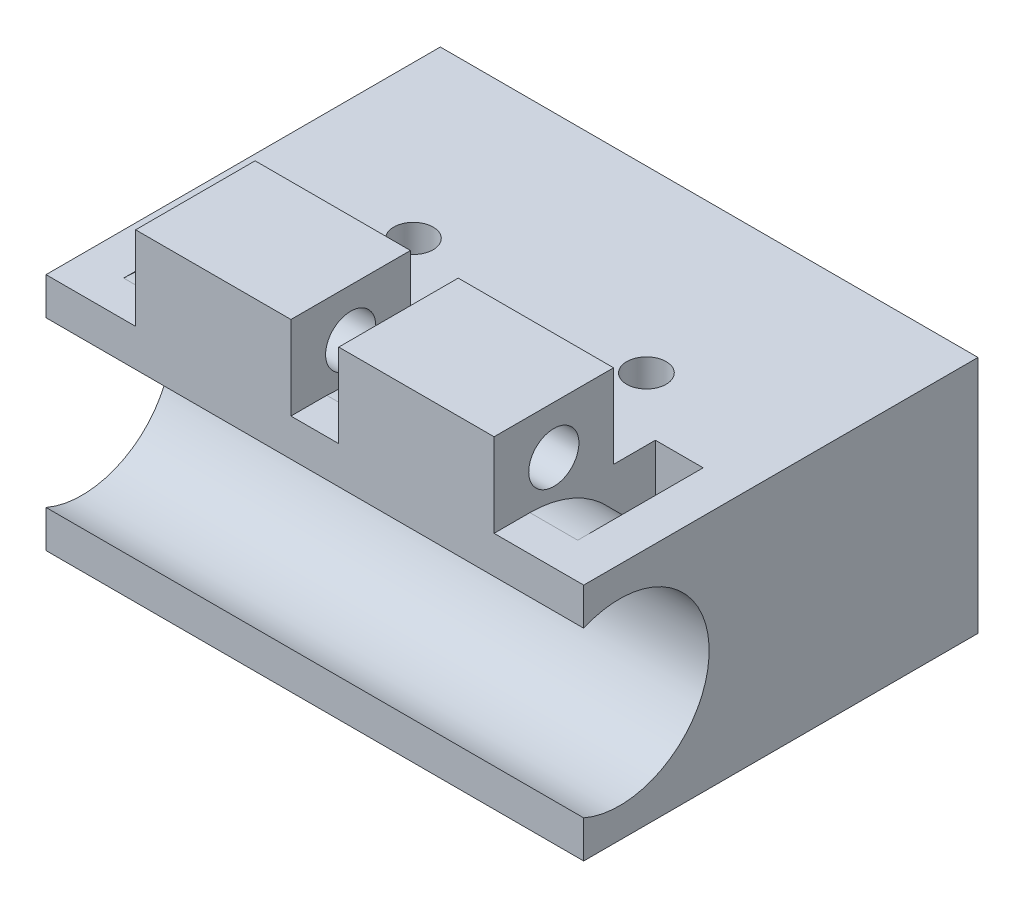
SolidWorks part; units mm, degrees
ref_plane "Front Plane" through (0, 0, 0) normal (0, 0, 1) x (1, 0, 0)
ref_plane "Top Plane" through (0, 0, 0) normal (0, 1, 0) x (1, 0, 0)
ref_plane "Right Plane" through (0, 0, 0) normal (1, 0, 0) x (0, 0, -1)
sketch "Sketch2" plane through (0, 0, 0) normal (0, 0, 1) x (1, 0, 0)
  line L1 (22.5, 10) -> (-22.5, 10)
  line L2 (22.5, 10) -> (22.5, -10)
  line L3 (22.5, -10) -> (-22.5, -10)
  line L4 (-22.5, 10) -> (-22.5, -10)
  line L5 (22.5, 10) -> (-22.5, -10) construction
  line L6 (22.5, -10) -> (-22.5, 10) construction
  point P0 (0, 0)
  dimension "D1" = 20
  dimension "D2" = 45
extrude "Boss-Extrude1" add sketch "Sketch2" along normal blind 33
sketch "Sketch3" plane through (22.5, 0, 0) normal (1, 0, 0) x (0, 0, -1)
  line L0 (-30, 0) -> (0, 0) construction
  circle A0 centre (-30, 0) radius 7.5
  dimension "D1" = 15
  dimension "D2" = 30
extrude "Cut-Extrude1" cut sketch "Sketch3" against normal blind 45
sketch "Sketch4" plane through (0, 0, 0) normal (0, 0, -1) x (-1, 0, 0)
  line L4 (22.5, -10) -> (22.5, 10)
  line L5 (22.5, 10) -> (-22.5, 10)
  line L6 (-22.5, 10) -> (-22.5, -10)
  line L7 (-22.5, -10) -> (22.5, -10)
  line L8 (22.5, -10) -> (22.5, 10)
  line L9 (22.5, 10) -> (-22.5, 10)
  line L10 (-22.5, 10) -> (-22.5, -10)
  line L11 (-22.5, -10) -> (22.5, -10)
  circle A0 centre (-15, 0) radius 4
  circle A1 centre (15, 0) radius 4
  dimension "D2" = 8
  dimension "D3" = 30
  dimension "D4" = 15
  dimension "D1" = 0
extrude "Cut-Extrude2" cut sketch "Sketch4" against normal blind 10 contours A0 | A1 region at (15, 0, 0) region at (-15, 0, 0)
sketch "Sketch5" plane through (0, -10, 0) normal (0, -1, 0) x (1, 0, 0)
  line L0 (0, 19.5) -> (0, 0) construction
  line L1 (-19, 21) -> (-15, 21)
  line L2 (-19, 21) -> (-19, 19.5)
  line L3 (-19, 19.5) -> (-15, 19.5)
  line L4 (-15, 21) -> (-15, 19.5)
  line L5 (-2, 19.5) -> (2, 19.5)
  line L6 (-2, 19.5) -> (-2, 21)
  line L7 (-2, 21) -> (2, 21)
  line L8 (2, 19.5) -> (2, 21)
  line L9 (15, 19.5) -> (19, 19.5)
  line L10 (15, 19.5) -> (15, 21)
  line L11 (15, 21) -> (19, 21)
  line L12 (19, 19.5) -> (19, 21)
  line L13 (-22.5, 19.5) -> (-19, 19.5) construction
  line L14 (-22.5, 33) -> (-22.5, 0) construction
  line L15 (-2, 19.5) -> (-15, 19.5) construction
  line L16 (2, 19.5) -> (15, 19.5) construction
  line L17 (19, 19.5) -> (22.5, 19.5) construction
  line L18 (22.5, 33) -> (22.5, 0) construction
  line L27 (-22.5, 0) -> (22.5, 0) construction
  dimension "D1" = 4
  dimension "D2" = 1.5
  dimension "D3" = 30
  dimension "D4" = 21
extrude "Cut-Extrude3" cut sketch "Sketch5" against normal blind 39
fillet "Fillet1" radius 9 3 edges at (17, -10, 21) (0, -10, 21) (-17, -10, 21)
hole_wizard "M4x0.7 Tapped Hole1" positions "Sketch7" profile "Sketch6" tap size "M4x0.7" standard "ANSI Metric" end condition through all
sketch "Sketch7" plane through (0, -10, 0) normal (0, -1, 0) x (-1, 0, 0)
  line L0 (0, 0) -> (0, -15) construction
  line L3 (9.75, -15) -> (-9.75, -15) construction
  point P0 (-9.75, -15)
  point P2 (9.75, -15)
  dimension "D1" = 19.5
  dimension "D2" = 15
cosmetic thread "Hole Thread1" parameters "D2"=4
cosmetic thread "Hole Thread2" parameters "D2"=4
sketch "Sketch6" plane through (9.75, -10, 15) normal (1, 0, 0) x (0, 0, -1)
  line L0 (0, 0) -> (0, 20)
  line L1 (0, 20) -> (1.65, 20)
  line L2 (1.65, 20) -> (1.65, 0)
  line L5 (1.65, 0) -> (0, 0)
  line L11 (0, -6.35) -> (0, 107.95) construction
  dimension "Thru Tap Drill Dia." = 3.3
  dimension "Thru Tap Drill Depth" = 20
sketch "Sketch8" plane through (0, -10, 0) normal (0, -1, 0) x (1, 0, 0)
  line L0 (-22.5, 33) -> (22.5, 33) construction
  line L1 (-15, 23) -> (-2, 23)
  line L2 (-15, 23) -> (-15, 33)
  line L3 (-15, 33) -> (-2, 33)
  line L4 (-2, 23) -> (-2, 33)
  line L5 (2, 23) -> (15, 23)
  line L6 (2, 23) -> (2, 33)
  line L7 (2, 33) -> (15, 33)
  line L8 (15, 23) -> (15, 33)
  line L9 (-15, 30) -> (-15, 21) construction
  line L13 (15, 21) -> (15, 30) construction
  line L14 (-2, 21) -> (-2, 30) construction
  dimension "D2" = 10
extrude "Boss-Extrude2" add sketch "Sketch8" along normal blind 7
sketch "Sketch14" plane through (-15, 0, 0) normal (-1, 0, 0) x (0, 0, 1)
  line L0 (33, -10) -> (0, -10) construction
  line L1 (28, -13) -> (28, -17) construction
  line L2 (33, -17) -> (23, -17) construction
  circle A0 centre (28, -13) radius 2.1
  dimension "D1" = 4.2
  dimension "D2" = 3
extrude "Cut-Extrude6" cut sketch "Sketch14" against normal through all
move or copy body "Body-Move/Copy1" bodies to move or copy 109 copy no rotation origin (0, -3.5, 0) rotation axis (0, 0, 1) rotation angle 180
